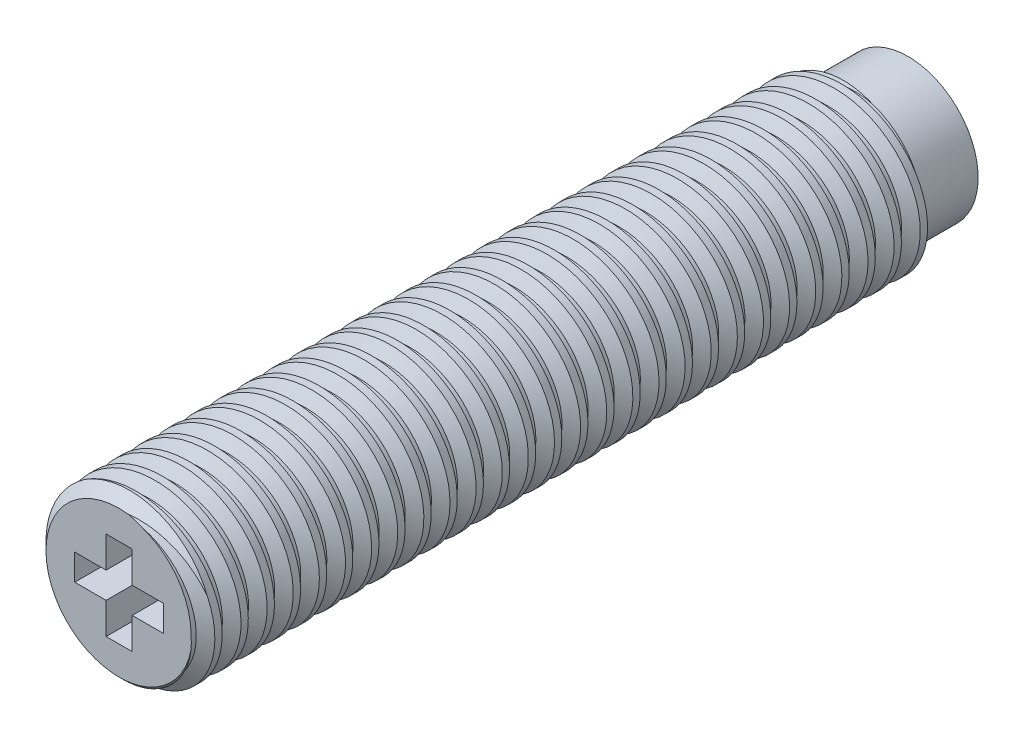
SolidWorks part; units mm, degrees
ref_plane "Front Plane" through (0, 0, 0) normal (0, 0, 1) x (1, 0, 0)
ref_plane "Top Plane" through (0, 0, 0) normal (0, 1, 0) x (1, 0, 0)
ref_plane "Right Plane" through (0, 0, 0) normal (1, 0, 0) x (0, 0, -1)
sketch "Sketch1" plane through (0, 0, 0) normal (0, 0, 1) x (1, 0, 0)
  circle A0 centre (0, 0) radius 8
  dimension "D1" = 16
extrude "Boss-Extrude1" add sketch "Sketch1" along normal blind 75.5
chamfer "Chamfer1" distance 1 angle 45 1 edges at (8, 0, 75.5)
ref_plane "Plane1" through (0, 0, 75.5) normal (0, 0, 1) x (1, 0, 0)
sketch "Sketch3" plane through (0, 0, 75.5) normal (0, 0, 1) x (1, 0, 0)
  circle A0 centre (0, 0) radius 8
sketch "Sketch4" plane through (0, 0, 0) normal (0, 1, 0) x (1, 0, 0)
  line L0 (-8.1701, -75.5) -> (-8.1701, -77.5)
  line L1 (-8.1701, -77.5) -> (-6.8701, -76.7494)
  line L2 (-6.8701, -76.7494) -> (-6.8701, -76.2506)
  line L3 (-6.8701, -76.2506) -> (-8.1701, -75.5)
  line L4 (-8, -74.5) -> (-8, -86.7444) construction
  line L5 (-8, -75.5) -> (8, -75.5) construction
  dimension "D1" = 2
  dimension "D2" = 1.3
  dimension "D3" = 60
curve "Helix/Spiral1" pitch 2.5 height 72.5 turns 29
sweep "Cut-Sweep2" cut profiles "Sketch4" path "Helix/Spiral1"
sketch "Sketch5" plane through (0, 0, 0) normal (0, 1, 0) x (1, 0, 0)
  line L0 (8, -2.1741) -> (8, 7.6033) construction
  line L1 (8, -4.3482) -> (8, 0) construction
  line L2 (8, 0) -> (-8, 0) construction
  line L3 (6.7, 0) -> (8, 0)
  line L4 (6.7, 0) -> (6.7, -5.5)
  line L5 (6.7, -5.5) -> (8, -5.5)
  line L6 (8, 0) -> (8, -5.5)
  dimension "D1" = 5.5
  dimension "D2" = 1.3
sweep "Cut-Sweep3" cut profiles "Sketch5" path edge at (8, 0, 0)
sketch "Sketch6" plane through (0, 0, 0) normal (0, 0, 1) x (1, 0, 0)
  line L1 (4, 2) -> (-4, 2)
  line L2 (4, 2) -> (4, -2)
  line L3 (4, -2) -> (-4, -2)
  line L4 (-4, 2) -> (-4, -2)
  point P4 (0, 2)
  point P5 (-4, 0)
  dimension "D1" = 8
  dimension "D2" = 4
extrude "Cut-Extrude1" cut sketch "Sketch6" along normal blind 8
sketch "Sketch7" plane through (0, 0, 0) normal (0, 0, 1) x (1, 0, 0)
  text T0 "<b>CW</b>" font "Century Gothic" height 2.5
extrude "Cut-Extrude2" cut sketch "Sketch7" along normal blind 1.5
sketch "Sketch8" plane through (0, 0, 75.5) normal (0, 0, 1) x (1, 0, 0)
  line L1 (-1.25, 4.25) -> (1.25, 4.25)
  line L2 (-1.25, 4.25) -> (-1.25, -4.25)
  line L3 (-1.25, -4.25) -> (1.25, -4.25)
  line L4 (1.25, 4.25) -> (1.25, -4.25)
  line L5 (-4.25, 1.25) -> (4.25, 1.25)
  line L6 (-4.25, 1.25) -> (-4.25, -1.25)
  line L7 (-4.25, -1.25) -> (4.25, -1.25)
  line L8 (4.25, 1.25) -> (4.25, -1.25)
  point P8 (0, 4.25)
  point P9 (1.25, 0)
  point P10 (0, 1.25)
  point P11 (4.25, 0)
  point P12 (0, 0)
  dimension "D1" = 2.5
  dimension "D2" = 2.5
  dimension "D3" = 8.5
  dimension "D4" = 8.5
extrude "Cut-Extrude3" cut sketch "Sketch8" against normal blind 11 contours L2 L5 L4 L1 | L2 L7 L4 L5 | L6 L7 L2 L5 | L8 L5 L4 L7 | L7 L2 L3 L4
